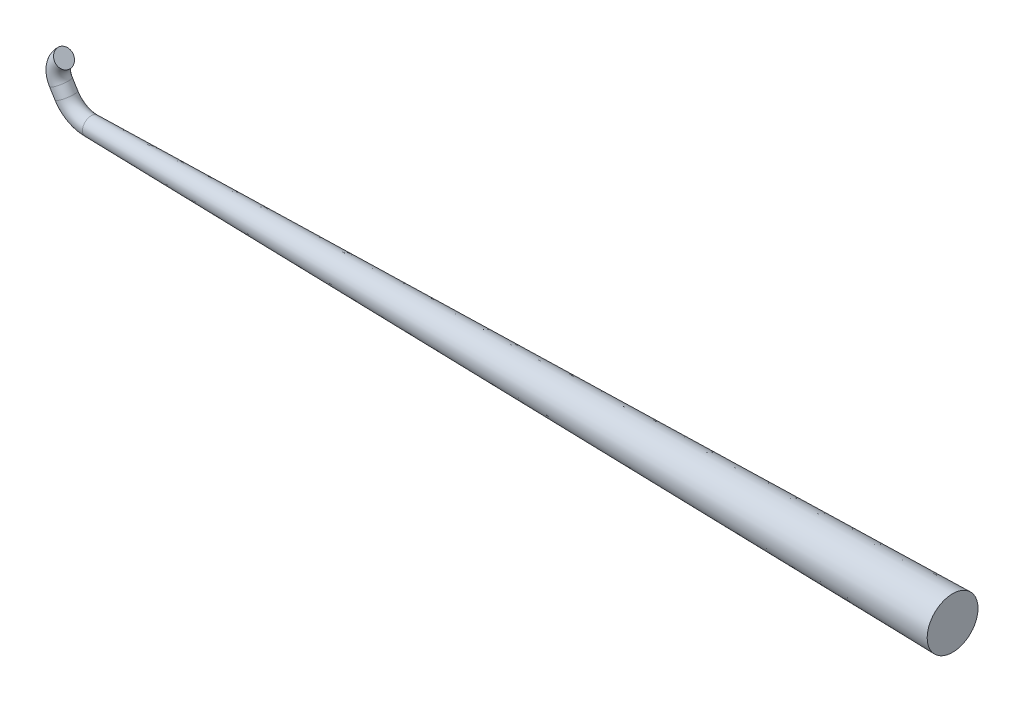
SolidWorks part; units mm, degrees
ref_plane "Front Plane" through (0, 0, 0) normal (0, 0, 1) x (1, 0, 0)
ref_plane "Top Plane" through (0, 0, 0) normal (0, 1, 0) x (1, 0, 0)
ref_plane "Right Plane" through (0, 0, 0) normal (1, 0, 0) x (0, 0, -1)
ref_axis "Axis1" through (-88.99, 0, 0) along (1, 0, 0)
sketch "Sketch1" plane through (0, 0, 0) normal (0, 0, 1) x (1, 0, 0)
  line L0 (-710.0186, -116.323) -> (-50.7383, -116.323) construction
  line L1 (-75.4839, 42.7016) -> (104.5161, 42.7016)
  line L2 (-30.3289, 22.3157) -> (-73.7125, 22.3157)
  line L3 (-74.9591, 23.0097) -> (-75.2364, 23.4571)
  line L4 (-73.7125, 22.754) -> (-73.7125, 22.3157)
  line L5 (-30.3289, 23.5956) -> (-30.3289, 22.3157)
  line L6 (-73.7125, 22.754) -> (-30.3289, 23.5956)
  line L7 (-30.3289, 22.3157) -> (59.7461, 22.3157)
  line L8 (-30.3289, 23.5956) -> (-30.1024, 23.5956)
  line L9 (-30.1024, 23.5956) -> (-29.3556, 24.0584)
  line L10 (-29.3556, 24.0584) -> (-19.1718, 24.3036)
  line L11 (-19.1718, 24.3036) -> (-14.4931, 24.5817)
  line L12 (-14.4931, 24.5817) -> (-8.1884, 24.5817)
  line L13 (-8.1884, 24.5817) -> (42.4258, 24.5817)
  line L14 (42.4258, 24.5817) -> (47.8681, 24.5817)
  line L15 (47.8681, 24.5817) -> (48.739, 24.5817)
  line L16 (48.739, 24.5817) -> (53.9231, 24.3036)
  line L17 (53.9231, 24.3036) -> (59.5111, 24.0584)
  line L18 (59.5111, 24.0584) -> (60.2536, 23.5956)
  line L19 (60.2536, 23.5956) -> (60.2536, 22.3157)
  line L20 (60.2536, 22.3157) -> (59.7461, 22.3157)
  arc A0 (-73.7125, 22.3157) -> (-74.9591, 23.0097) centre (-73.7125, 23.7823) cw
  arc A1 (-75.2364, 23.4571) -> (-75.0806, 24.5817) centre (-74.4806, 23.9255) cw
  dimension "D1" = 180
sketch "Sketch8" plane through (0, 0, 0) normal (0, 0, 1) x (1, 0, 0)
  line L4 (-30.3289, 22.3157) -> (-73.7125, 22.3157) construction
  line L5 (-30.3289, 23.5956) -> (-30.3289, 22.3157) construction
  line L6 (-73.7125, 22.754) -> (-30.3289, 23.5956) construction
  line L7 (-73.7125, 22.754) -> (-73.7125, 22.3157) construction
  line L8 (-30.3289, 22.3157) -> (-73.7125, 22.3157)
  line L9 (-30.3289, 23.5956) -> (-30.3289, 22.3157)
  line L10 (-73.7125, 22.754) -> (-30.3289, 23.5956)
  line L11 (-73.7125, 22.754) -> (-73.7125, 22.3157)
revolve "Revolve1" add sketch "Sketch8" angle 360 about L8
sketch "Sketch9" plane through (-73.7125, 0, 0) normal (-1, 0, 0) x (0, 0, 1)
  circle A0 centre (0, 22.3157) radius 0.4383 construction
  circle A1 centre (0, 22.3157) radius 0.4383
sweep "Sweep1" add profiles "Sketch9" path "Sketch1"
ref_plane "Plane1" through (-30.3289, 0, 0) normal (1, 0, 0) x (0, 0, -1)
ref_plane "Plane2" through (-73.7125, 0, 0) normal (1, 0, 0) x (0, 0, -1)
sketch "Sketch5" plane through (-30.3289, 0, 0) normal (1, 0, 0) x (0, 0, -1)
  circle A0 centre (0, 22.3157) radius 1.25
  dimension "D1" = 2.5
sketch "Sketch6" plane through (-73.7125, 0, 0) normal (1, 0, 0) x (0, 0, -1)
  line L0 (0, 22.754) -> (0, 22.3157) construction
  circle A0 centre (0, 22.5349) radius 0.415
  dimension "D1" = 0.83
